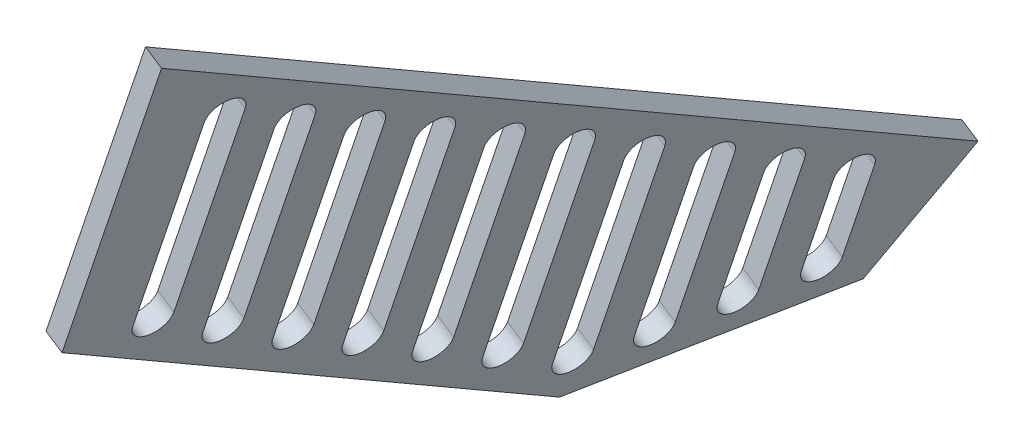
SolidWorks part; units mm, degrees
ref_plane "Front Plane" through (0, 0, 0) normal (1, 0, 0) x (0, 1, 0)
ref_plane "Top Plane" through (0, 0, 0) normal (0, 0, 1) x (0, 1, 0)
ref_plane "Right Plane" through (0, 0, 0) normal (0, 1, 0) x (-1, 0, 0)
sketch "Sketch1" plane through (905.1382, -304.2208, 175.6419) normal (0.9323, -0.3133, 0.1809) x (0.3076, 0.9496, 0.0597)
  line L10 (1336.6032, 823.3629) -> (1336.6032, 786.9221)
  line L11 (1336.6032, 786.9221) -> (1353.1721, 776.6609)
  line L12 (1353.1721, 776.6609) -> (1422.9724, 889.3682)
  line L13 (1422.9724, 889.3682) -> (1379.1316, 892.0339)
  line L14 (1379.1316, 892.0339) -> (1336.6032, 823.3629)
  line L15 (1336.6032, 823.3629) -> (1336.6032, 786.9221)
  line L16 (1336.6032, 786.9221) -> (1353.1721, 776.6609)
  line L17 (1353.1721, 776.6609) -> (1422.9724, 889.3682)
  line L18 (1422.9724, 889.3682) -> (1379.1316, 892.0339)
  line L19 (1379.1316, 892.0339) -> (1336.6032, 823.3629)
  dimension "D1" = 0
extrude "Boss-Extrude1" add sketch "Sketch1" along normal blind 3
sketch "Sketch2" plane through (907.9349, -305.1608, 176.1847) normal (0.9323, -0.3133, 0.1809) x (0.3076, 0.9496, 0.0597)
  line L0 (1372.635, 868.8473) -> (1404.0068, 866.9399)
  line L7 (1372.9385, 873.8381) -> (1404.3102, 871.9306)
  line L8 (1372.7868, 871.3427) -> (1404.1585, 869.4353) construction
  line L9 (1366.6557, 859.1924) -> (1398.0274, 857.285)
  line L10 (1366.9591, 864.1832) -> (1398.3309, 862.2757)
  line L11 (1378.7661, 880.9976) -> (1410.1378, 879.0902) construction
  line L12 (1378.9178, 883.493) -> (1410.2896, 881.5856)
  line L13 (1378.6144, 878.5022) -> (1409.9861, 876.5948)
  line L14 (1366.8074, 861.6878) -> (1398.1792, 859.7803) construction
  line L15 (1360.6763, 849.5375) -> (1392.0481, 847.63)
  line L16 (1360.9798, 854.5283) -> (1392.3515, 852.6208)
  line L17 (1360.8281, 852.0329) -> (1392.1998, 850.1254) construction
  line L18 (1354.697, 839.8826) -> (1386.0687, 837.9751)
  line L19 (1355.0005, 844.8734) -> (1386.3722, 842.9659)
  line L20 (1354.8487, 842.378) -> (1386.2205, 840.4705) construction
  line L21 (1348.7177, 830.2277) -> (1380.0894, 828.3202)
  line L22 (1349.0211, 835.2185) -> (1380.3928, 833.311)
  line L23 (1348.8694, 832.7231) -> (1380.2411, 830.8156) construction
  line L24 (1380.7385, 888.9306) -> (1339.6032, 822.5092)
  line L25 (1339.6032, 822.5092) -> (1339.6032, 788.5929)
  line L26 (1339.6032, 788.5929) -> (1352.2011, 780.791)
  line L27 (1352.2011, 780.791) -> (1417.778, 886.6785)
  line L28 (1417.778, 886.6785) -> (1380.7385, 888.9306)
  line L29 (1380.7385, 888.9306) -> (1339.6032, 822.5092) construction
  line L30 (1339.6032, 822.5092) -> (1339.6032, 788.5929) construction
  line L31 (1339.6032, 788.5929) -> (1352.2011, 780.791) construction
  line L32 (1352.2011, 780.791) -> (1417.778, 886.6785) construction
  line L33 (1417.778, 886.6785) -> (1380.7385, 888.9306) construction
  line L34 (1342.7383, 820.5728) -> (1374.11, 818.6653)
  line L35 (1343.0418, 825.5636) -> (1374.4135, 823.6561)
  line L36 (1342.89, 823.0682) -> (1374.2618, 821.1607) construction
  line L39 (1342.1032, 793.0606) -> (1356.3237, 792.196) construction
  line L40 (1342.1032, 813.0976) -> (1368.2824, 811.5058) construction
  line L41 (1342.255, 815.5929) -> (1368.4341, 814.0012)
  line L42 (1341.9515, 810.6022) -> (1368.1307, 809.0104)
  line L43 (1342.1032, 803.0791) -> (1362.3031, 801.8509) construction
  line L44 (1342.255, 805.5745) -> (1362.4548, 804.3463)
  line L45 (1341.9515, 800.5837) -> (1362.1513, 799.3555)
  line L46 (1337.0624, 815.9087) -> (1368.4341, 814.0012) [skipped]
  line L47 (1336.759, 810.9179) -> (1368.1307, 809.0104) [skipped]
  line L48 (1342.255, 795.556) -> (1356.4755, 794.6914)
  line L49 (1341.9515, 790.5652) -> (1356.172, 789.7006)
  line L50 (1349.0618, 790.1329) -> (1345.7504, 784.786) construction
  line L53 (1394.6037, 882.5393) -> (1397.9151, 887.8862) construction
  arc A0 (1378.9178, 883.493) -> (1378.6144, 878.5022) centre (1378.7661, 880.9976) ccw
  arc A1 (1409.9861, 876.5948) -> (1410.2896, 881.5856) centre (1410.1378, 879.0902) ccw
  arc A2 (1372.9385, 873.8381) -> (1372.635, 868.8473) centre (1372.7868, 871.3427) ccw
  arc A3 (1404.0068, 866.9399) -> (1404.3102, 871.9306) centre (1404.1585, 869.4353) ccw
  arc A4 (1366.9591, 864.1832) -> (1366.6557, 859.1924) centre (1366.8074, 861.6878) ccw
  arc A5 (1398.0274, 857.285) -> (1398.3309, 862.2757) centre (1398.1792, 859.7803) ccw
  arc A6 (1360.9798, 854.5283) -> (1360.6763, 849.5375) centre (1360.8281, 852.0329) ccw
  arc A7 (1392.0481, 847.63) -> (1392.3515, 852.6208) centre (1392.1998, 850.1254) ccw
  arc A8 (1355.0005, 844.8734) -> (1354.697, 839.8826) centre (1354.8487, 842.378) ccw
  arc A9 (1386.0687, 837.9751) -> (1386.3722, 842.9659) centre (1386.2205, 840.4705) ccw
  arc A10 (1349.0211, 835.2185) -> (1348.7177, 830.2277) centre (1348.8694, 832.7231) ccw
  arc A11 (1380.0894, 828.3202) -> (1380.3928, 833.311) centre (1380.2411, 830.8156) ccw
  arc A12 (1343.0418, 825.5636) -> (1342.7383, 820.5728) centre (1342.89, 823.0682) ccw
  arc A13 (1374.11, 818.6653) -> (1374.4135, 823.6561) centre (1374.2618, 821.1607) ccw
  arc A16 (1342.255, 815.5929) -> (1341.9515, 810.6022) centre (1342.1032, 813.0976) ccw
  arc A17 (1368.1307, 809.0104) -> (1368.4341, 814.0012) centre (1368.2824, 811.5058) ccw
  arc A18 (1342.255, 805.5745) -> (1341.9515, 800.5837) centre (1342.1032, 803.0791) ccw
  arc A19 (1362.1513, 799.3555) -> (1362.4548, 804.3463) centre (1362.3031, 801.8509) ccw
  arc A20 (1337.0624, 815.9087) -> (1336.759, 810.9179) centre (1336.9107, 813.4133) ccw [skipped]
  arc A21 (1368.1307, 809.0104) -> (1368.4341, 814.0012) centre (1368.2824, 811.5058) ccw [skipped]
  arc A22 (1342.255, 795.556) -> (1341.9515, 790.5652) centre (1342.1032, 793.0606) ccw
  arc A23 (1356.172, 789.7006) -> (1356.4755, 794.6914) centre (1356.3237, 792.196) ccw
  point P2 (1394.452, 880.0439)
  point P10 (1388.4726, 870.389)
  point P19 (1382.4933, 860.7341)
  point P29 (1376.5139, 851.0792)
  point P36 (1370.5346, 841.4243)
  point P43 (1364.5552, 831.7694)
  point P50 (1358.5759, 822.1144)
  point P55 (1349.2135, 792.6283)
  point P63 (1355.1928, 812.3017)
  point P70 (1352.2032, 802.465)
  dimension "D1" = 3
  dimension "D2" = 8
  dimension "D3" = 5
  dimension "D4" = 5
  dimension "D5" = 5
  dimension "D6" = 5
  dimension "D7" = 5
  dimension "D8" = 5
  dimension "D9" = 5
  dimension "D10" = 5
extrude "Cut-Extrude1" cut sketch "Sketch2" against normal blind 3
